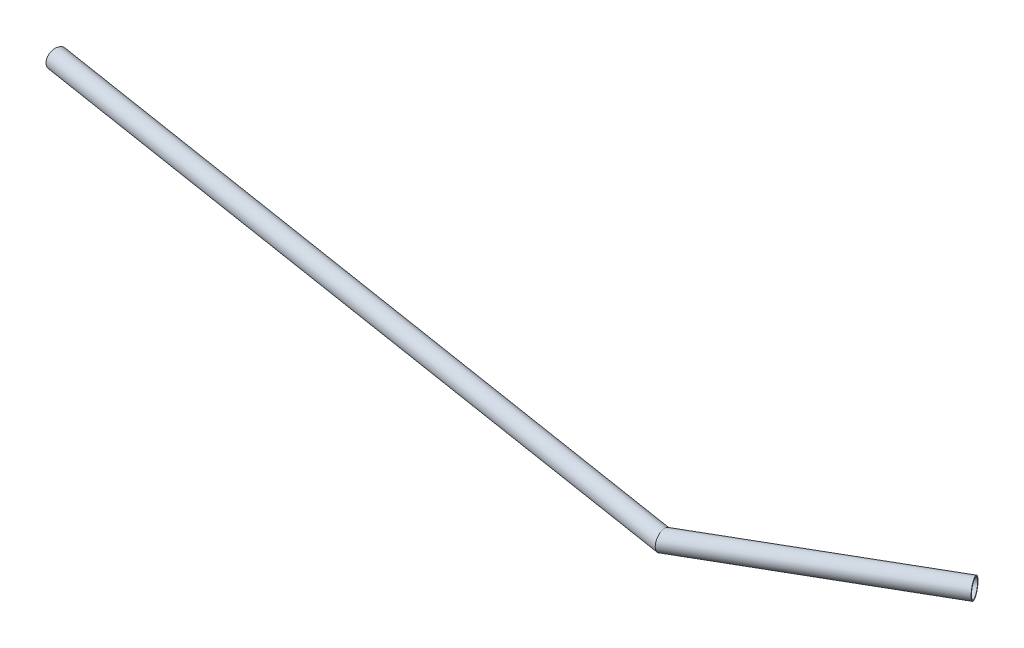
SolidWorks part; units mm, degrees
ref_plane "Front Plane" through (0, 0, 0) normal (0, 0, 1) x (1, 0, 0)
ref_plane "Top Plane" through (0, 0, 0) normal (0, 1, 0) x (1, 0, 0)
ref_plane "Right Plane" through (0, 0, 0) normal (1, 0, 0) x (0, 0, -1)
sketch "Sketch1" plane through (0, 0, 0) normal (0, 1, 0) x (1, 0, 0)
  line L0 (-465, 0) -> (465, 0) construction
  line L1 (465, 0) -> (265, -115.4701)
  line L2 (-465, 0) -> (265, -115.4701)
  point P3 (0, 0)
  dimension "D1" = 930
  dimension "D2" = 30
  dimension "D3" = 200
ref_plane "Plane1" through (-465, 0, 0) normal (0.9877, 0, 0.1562) x (0.1562, 0, -0.9877)
sketch "Sketch2" plane through (-465, 0, 0) normal (0.9877, 0, 0.1562) x (0.1562, 0, -0.9877)
  line L0 (0, 0) -> (145.2992, 0) construction
  line L1 (145.2992, 0) -> (0, 0) construction
  circle A0 centre (0, 0) radius 9.525
  dimension "D1" = 19.05
sweep "Sweep-Thin1" add profiles "Sketch2" path "Sketch1" parameters "D1"=1
